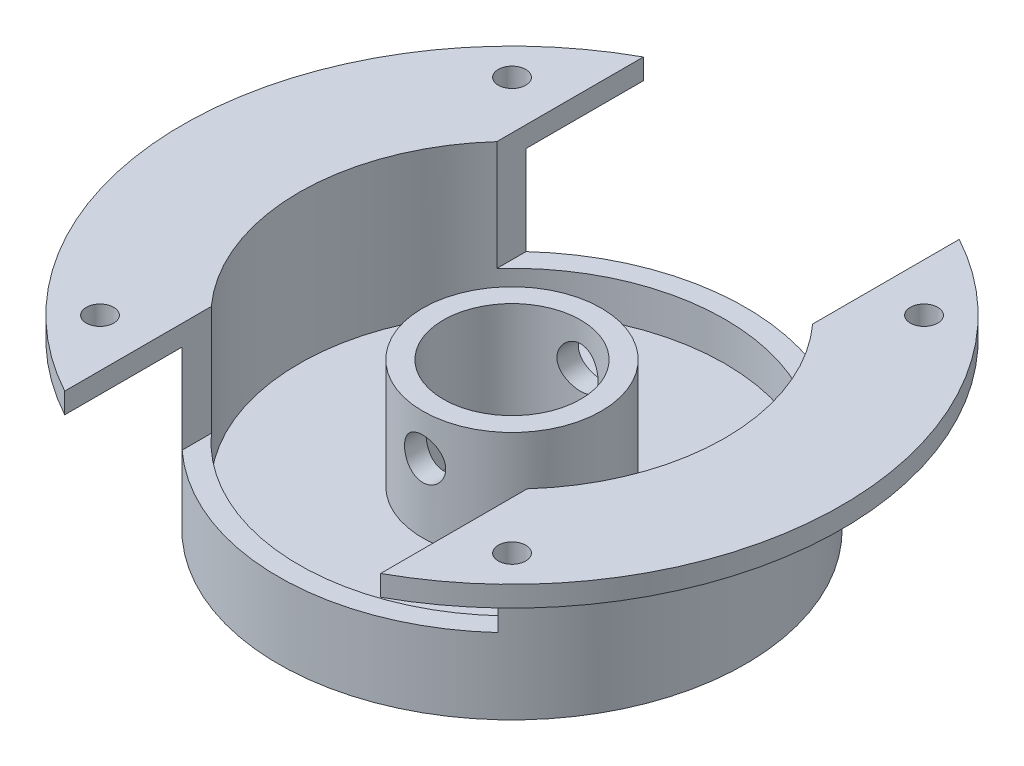
SolidWorks part; units mm, degrees
ref_plane "前视基准面" through (0, 0, 0) normal (0, 0, 1) x (1, 0, 0)
ref_plane "上视基准面" through (0, 0, 0) normal (0, 1, 0) x (1, 0, 0)
ref_plane "右视基准面" through (0, 0, 0) normal (1, 0, 0) x (0, 0, -1)
sketch "草图2" plane through (0, 0, 0) normal (0, 1, 0) x (1, 0, 0)
  line L0 (-15, 15) -> (15, 15) construction
  line L1 (0, 0) -> (0, -31.7144) construction
  line L2 (-15, 15) -> (-15, -28.2858) construction
  line L3 (15, 15) -> (15, -29.3473) construction
  circle A0 centre (0, 0) radius 24
  circle A1 centre (0, 0) radius 15.5
  circle A7 centre (-15, 15) radius 1
  circle A8 centre (15, 15) radius 1
  circle A9 centre (0, 0) radius 21.2132 construction
  circle A10 centre (-15, -15) radius 1
  circle A11 centre (15, -15) radius 1
  point P14 (15, -17.4707)
  point P16 (-15, -13.9962)
  point P18 (0, 2.9054)
  point P21 (0, -0.421)
  dimension "D1" = 31
  dimension "D2" = 48
  dimension "D3" = 2
  dimension "D4" = 2
  dimension "D5" = 2
  dimension "D6" = 2
  dimension "D7" = 30
  dimension "D8" = 30
extrude "凸台-拉伸1" add sketch "草图2" along normal blind 1.5
sketch "草图4" plane through (0, 0, 0) normal (0, -1, 0) x (1, 0, 0)
  circle A0 centre (0, 0) radius 15.5 construction
  circle A1 centre (0, 0) radius 15.5
  circle A2 centre (0, 0) radius 17
  dimension "D1" = 1.5
extrude "凸台-拉伸3" add sketch "草图4" along normal blind 12
sketch "草图5" plane through (0, -12, 0) normal (0, -1, 0) x (1, 0, 0)
  circle A0 centre (0, 0) radius 17 construction
  circle A1 centre (0, 0) radius 17
  circle A2 centre (0, 0) radius 5
  dimension "D1" = 10
extrude "凸台-拉伸4" add sketch "草图5" against normal blind 1.5 from offset 1.2 offset against normal yes
sketch "草图6" plane through (0, 1.5, 0) normal (0, 1, 0) x (1, 0, 0)
  line L0 (0, -26.512) -> (0, 26.5739) construction
  line L1 (-11.5, 24) -> (11.5, 24)
  line L2 (11.5, 24) -> (11.5, -24)
  line L3 (11.5, -24) -> (-11.5, -24)
  line L4 (-11.5, 24) -> (-11.5, -24)
  circle A0 centre (0, 0) radius 24 construction
  point P10 (0, -24)
  point P11 (0, 24)
  dimension "D1" = 23
extrude "切除-拉伸1" cut sketch "草图6" against normal blind 8
sketch "草图7" plane through (0, -9.3, 0) normal (0, 1, 0) x (1, 0, 0)
  circle A0 centre (0, 0) radius 5 construction
  circle A1 centre (0, 0) radius 5
  circle A2 centre (0, 0) radius 6.5
  dimension "D1" = 1.5
extrude "凸台-拉伸5" add sketch "草图7" along normal blind 8
sketch "草图8" plane through (0, 0, 0) normal (0, 0, 1) x (1, 0, 0)
  line L0 (0, 0) -> (0, -17.8099) construction
  line L1 (5, -1.3) -> (-5, -1.3) construction
  circle A0 centre (0, -4.3) radius 1.5
  dimension "D1" = 3
  dimension "D2" = 3
extrude "切除-拉伸2" cut sketch "草图8" against normal blind 10 and the other way blind 10
